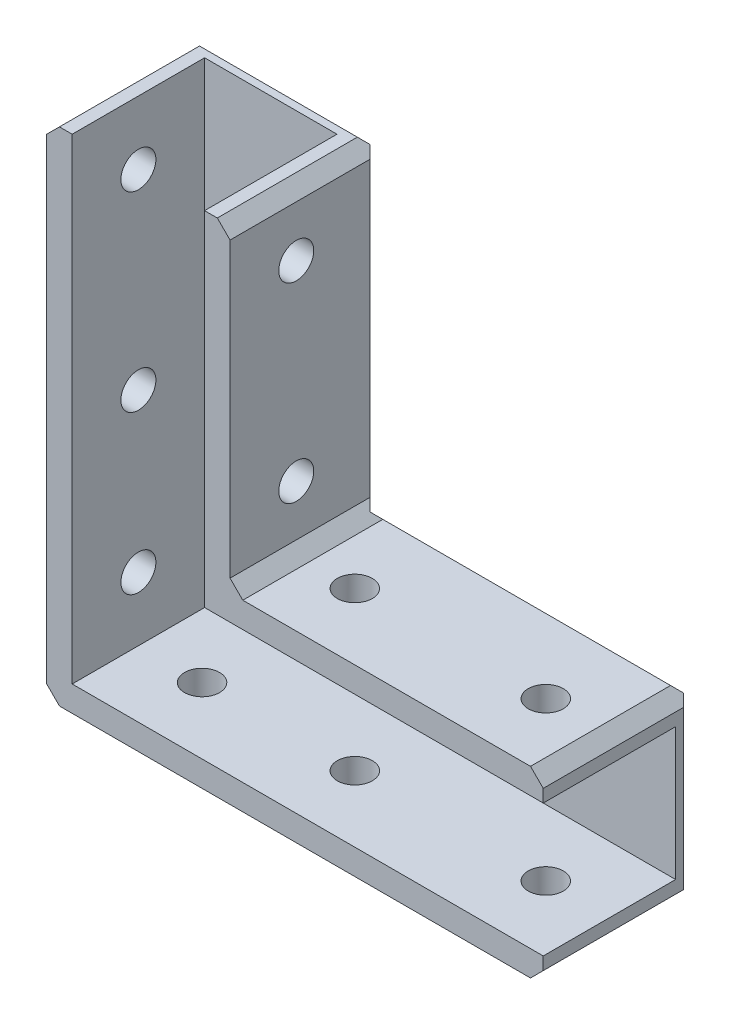
SolidWorks part; units mm, degrees
ref_plane "Plan de face" through (0, 0, 0) normal (0, 0, 1) x (1, 0, 0)
ref_plane "Plan de dessus" through (0, 0, 0) normal (0, 1, 0) x (1, 0, 0)
ref_plane "Plan de droite" through (0, 0, 0) normal (1, 0, 0) x (0, 0, -1)
sketch "Esquisse2" plane through (0, 0, 0) normal (0, 0, 1) x (1, 0, 0)
  line L1 (0, 0) -> (78, 0)
  line L2 (0, 0) -> (0, 28.8)
  line L3 (0, 28.8) -> (78, 28.8)
  line L4 (78, 0) -> (78, 28.8)
  line L5 (0, 28.8) -> (28.8, 28.8)
  line L6 (0, 28.8) -> (0, 78.8)
  line L7 (0, 78.8) -> (28.8, 78.8)
  line L8 (28.8, 28.8) -> (28.8, 78.8)
  dimension "D1" = 78
  dimension "D2" = 28.8
  dimension "D3" = 50
  dimension "D4" = 28.8
extrude "Boss.-Extru.2" add sketch "Esquisse2" along normal blind 24 contours L3 L8 L7 L6 | L1 L4 L3 L2 region at (39, 14.4, 0) region at (14.4, 53.8, 0)
sketch "Esquisse3" plane through (0, 0, 24) normal (0, 0, 1) x (1, 0, 0)
  line L0 (4, 78.8) -> (4, 4)
  line L1 (0, 78.8) -> (28.8, 78.8) construction
  line L2 (4, 4) -> (78, 4)
  line L3 (78, 0) -> (78, 28.8) construction
  line L4 (78, 24.8) -> (24.8, 24.8)
  line L5 (24.8, 24.8) -> (24.8, 78.8)
  line L6 (0, 0) -> (78, 0) construction
  line L7 (0, 0) -> (0, 78.8) construction
  line L8 (28.8, 28.8) -> (28.8, 78.8) construction
  line L9 (28.8, 28.8) -> (78, 28.8) construction
  line L10 (78, 4) -> (78, 24.8)
  line L11 (4, 78.8) -> (24.8, 78.8)
  dimension "D1" = 4
  dimension "D2" = 4
  dimension "D3" = 4
  dimension "D4" = 4
extrude "Enlèv. mat.-Extru.1" cut sketch "Esquisse3" against normal blind 20.8
sketch "Esquisse4" plane through (0, 28.8, 0) normal (0, 1, 0) x (1, 0, 0)
  line L0 (28.8, -24) -> (78, -24) construction
  line L1 (78, -24) -> (78, 0) construction
  line L2 (28.8, -24) -> (28.8, 0) construction
  circle A0 centre (68, -13.6) radius 2.75
  circle A1 centre (38, -13.6) radius 2.75
  dimension "D1" = 5.5
  dimension "D2" = 5.5
  dimension "D3" = 30
  dimension "D4" = 10.4
  dimension "D5" = 10
  dimension "D6" = 10.4
  dimension "D7" = 9.2
extrude "Enlèv. mat.-Extru.2" cut sketch "Esquisse4" against normal blind 31.3893
sketch "Esquisse5" plane through (28.8, 0, 0) normal (1, 0, 0) x (0, 0, -1)
  line L0 (-24, 28.8) -> (-24, 78.8) construction
  line L1 (-24, 28.8) -> (0, 28.8) construction
  line L2 (-24, 78.8) -> (0, 78.8) construction
  circle A0 centre (-13.6, 38.8) radius 2.75
  circle A1 centre (-13.6, 68.8) radius 2.75
  point P8 (-12, 28.8)
  dimension "D1" = 5.5
  dimension "D2" = 5.5
  dimension "D3" = 30
  dimension "D4" = 10.4
  dimension "D5" = 10.4
  dimension "D6" = 10
  dimension "D7" = 10
extrude "Enlèv. mat.-Extru.3" cut sketch "Esquisse5" against normal blind 31.3893
sketch "Esquisse6" plane through (0, 0, 0) normal (-1, 0, 0) x (0, 0, 1)
  line L0 (24, 0) -> (24, 78.8) construction
  line L1 (24, 0) -> (0, 0) construction
  circle A0 centre (13.6, 14) radius 2.75
  dimension "D3" = 5.5
  dimension "D1" = 10.4
  dimension "D2" = 14
extrude "Enlèv. mat.-Extru.4" cut sketch "Esquisse6" against normal blind 31.3893
sketch "Esquisse7" plane through (0, 0, 0) normal (0, -1, 0) x (1, 0, 0)
  line L0 (0, 24) -> (78, 24) construction
  line L1 (0, 24) -> (0, 0) construction
  circle A0 centre (14, 13.6) radius 2.75
  dimension "D1" = 5.5
  dimension "D2" = 10.4
  dimension "D3" = 14
extrude "Enlèv. mat.-Extru.5" cut sketch "Esquisse7" against normal blind 31.3893 contours A0
chamfer "Chanfrein1" distance 2 angle 45 4 edges at (28.8, 53.8, 0) (53.4, 28.8, 0) (39, 0, 0) (0, 39.4, 0)
chamfer "Chanfrein2" distance 2 angle 45 8 edges at (28.8, 28.8, 13) (0, 0, 13) (0, 78.8, 13) (14.4, 78.8, 0) (28.8, 78.8, 13) (78, 28.8, 13) (78, 14.4, 0) (78, 0, 13)
